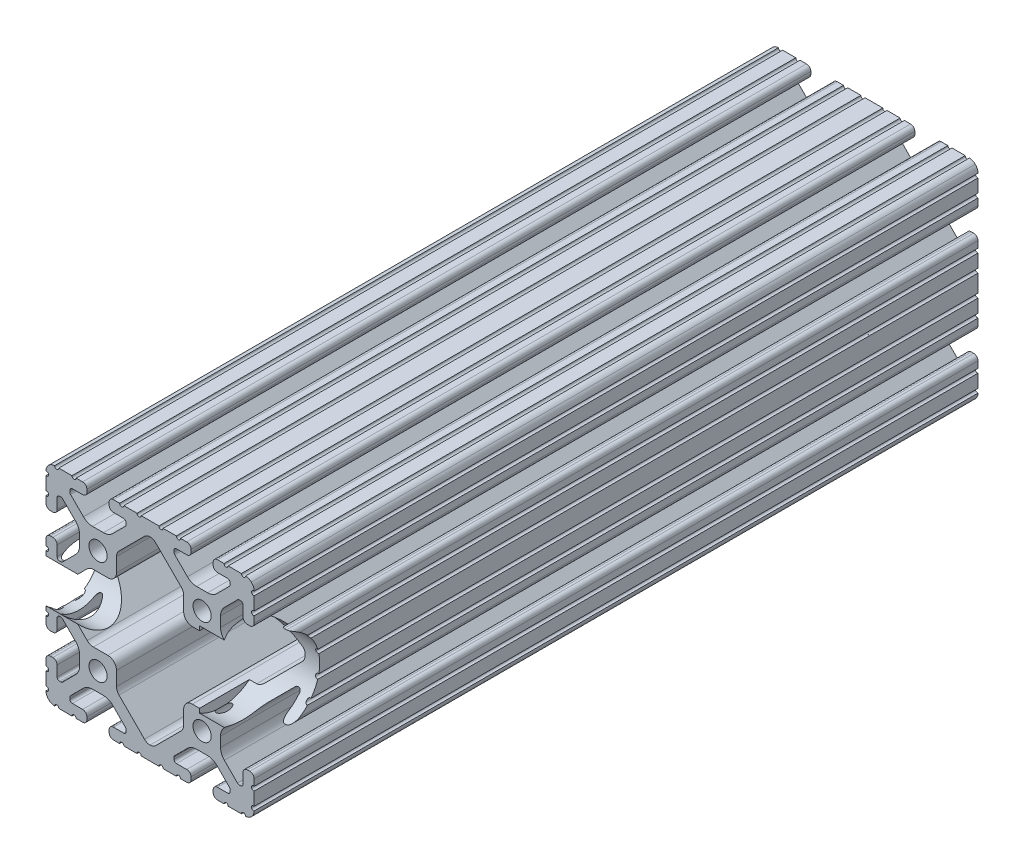
SolidWorks part; units mm, degrees
ref_plane "Front Plane" through (0, 0, 0) normal (0, 0, 1) x (1, 0, 0)
ref_plane "Top Plane" through (0, 0, 0) normal (0, 1, 0) x (1, 0, 0)
ref_plane "Right Plane" through (0, 0, 0) normal (1, 0, 0) x (0, 0, -1)
sketch "Sketch1" plane through (0, 0, 0) normal (0, 0, 1) x (1, 0, 0)
  line L0 (0, 38.1) -> (0, -38.1) construction
  line L1 (-38.1, -38.1) -> (38.1, -38.1) construction
  line L2 (-38.1, -38.1) -> (-38.1, 38.1) construction
  line L3 (-38.1, 38.1) -> (38.1, 38.1) construction
  line L4 (38.1, -38.1) -> (38.1, 38.1) construction
  line L5 (0, 38.1) -> (0, -38.1) construction
  line L6 (-38.1, 0) -> (38.1, 0) construction
  line L7 (-19.05, 19.05) -> (19.05, 19.05) construction
  line L8 (-19.05, 19.05) -> (-19.05, -19.05) construction
  line L9 (-19.05, -19.05) -> (19.05, -19.05) construction
  line L10 (19.05, 19.05) -> (19.05, -19.05) construction
  line L11 (-23.114, 38.1) -> (-23.114, -38.1) construction
  line L12 (-23.114, -38.1) -> (-14.986, 38.1) construction
  line L13 (-14.986, 38.1) -> (-14.986, -38.1) construction
  circle A0 centre (19.05, 19.05) radius 3.3274
  point P0 (0, 0)
  point P9 (0, 0)
  point P12 (-19.05, 0)
  line B0 (-11.3637, -22.8433) -> (-2.0515, -32.1555)
  line B1 (-12.2936, -15.4686) -> (-12.2936, -20.5983)
  line B2 (-20.769, -12.2936) -> (-15.4686, -12.2936)
  line B3 (-31.9021, -2.4756) -> (-23.0141, -11.3637)
  line B4 (-23.0141, 11.3637) -> (-31.9021, 2.4756)
  line B5 (-15.4686, 12.2936) -> (-20.769, 12.2936)
  line B6 (-12.2936, 20.5983) -> (-12.2936, 15.4686)
  line B7 (-2.0515, 32.1555) -> (-11.3637, 22.8433)
  line B8 (11.3637, 22.8433) -> (2.0515, 32.1555)
  line B9 (12.2936, 15.4686) -> (12.2936, 20.5983)
  line B10 (20.769, 12.2936) -> (15.4686, 12.2936)
  line B11 (31.9021, 2.4756) -> (23.0141, 11.3637)
  line B12 (23.0141, -11.3637) -> (31.9021, -2.4756)
  line B13 (15.4686, -12.2936) -> (20.769, -12.2936)
  line B14 (12.2936, -20.5983) -> (12.2936, -15.4686)
  line B15 (2.0515, -32.1555) -> (11.3637, -22.8433)
  line B16 (-4.7773, 38.1) -> (-9.6053, 38.1)
  line B17 (-11.1289, 38.1) -> (-13.4112, 38.1)
  line B18 (-14.986, 36.5252) -> (-14.986, 35.6108)
  line B19 (-13.4112, 34.036) -> (-9.652, 34.036)
  line B20 (-8.763, 33.147) -> (-8.763, 32.4935)
  line B21 (-9.0234, 31.8649) -> (-13.6907, 27.1976)
  line B22 (-17.0493, 25.8064) -> (-21.0507, 25.8064)
  line B23 (-24.4093, 27.1976) -> (-29.1002, 31.8885)
  line B24 (-29.337, 32.7207) -> (-29.337, 33.147)
  line B25 (-28.448, 34.036) -> (-24.6888, 34.036)
  line B26 (-23.114, 35.6108) -> (-23.114, 36.5252)
  line B27 (-24.6888, 38.1) -> (-27.0772, 38.1)
  line B28 (-28.6011, 38.1) -> (-33.4288, 38.1)
  line B29 (-38.1, 33.373) -> (-38.1, 28.5453)
  line B30 (-38.1, 27.0238) -> (-38.1, 24.6302)
  line B31 (-36.5252, 23.0554) -> (-35.6108, 23.0554)
  line B32 (-34.036, 24.6302) -> (-34.036, 28.448)
  line B33 (-33.147, 29.337) -> (-32.6643, 29.337)
  line B34 (-32.0357, 29.0766) -> (-27.1976, 24.2385)
  line B35 (-25.8064, 20.8799) -> (-25.8064, 17.2201)
  line B36 (-27.1976, 13.8615) -> (-31.9489, 9.1101)
  line B37 (-32.7869, 8.763) -> (-33.0603, 8.763)
  line B38 (-34.036, 9.7387) -> (-34.036, 13.4698)
  line B39 (-35.6108, 15.0446) -> (-36.5252, 15.0446)
  line B40 (-38.1, 13.4698) -> (-38.1, 11.075)
  line B41 (-38.1, 9.552) -> (-38.1, 4.7238)
  line B42 (-38.1, 3.2007) -> (-38.1, -3.2007)
  line B43 (-38.1, -4.7238) -> (-38.1, -9.552)
  line B44 (-38.1, -11.075) -> (-38.1, -13.4698)
  line B45 (-36.5252, -15.0446) -> (-35.6108, -15.0446)
  line B46 (-34.036, -13.4698) -> (-34.036, -9.7387)
  line B47 (-33.0603, -8.763) -> (-32.7869, -8.763)
  line B48 (-31.9489, -9.1101) -> (-27.1976, -13.8615)
  line B49 (-25.8064, -17.2201) -> (-25.8064, -20.8799)
  line B50 (-27.1976, -24.2385) -> (-32.0357, -29.0766)
  line B51 (-32.6643, -29.337) -> (-33.147, -29.337)
  line B52 (-34.036, -28.448) -> (-34.036, -24.6302)
  line B53 (-35.6108, -23.0554) -> (-36.5252, -23.0554)
  line B54 (-38.1, -24.6302) -> (-38.1, -27.0238)
  line B55 (-38.1, -28.5453) -> (-38.1, -33.373)
  line B56 (-33.4288, -38.1) -> (-28.6011, -38.1)
  line B57 (-27.0772, -38.1) -> (-24.6888, -38.1)
  line B58 (-23.114, -36.5252) -> (-23.114, -35.6108)
  line B59 (-24.6888, -34.036) -> (-28.448, -34.036)
  line B60 (-29.337, -33.147) -> (-29.337, -32.7207)
  line B61 (-29.1002, -31.8885) -> (-24.4093, -27.1976)
  line B62 (-21.0507, -25.8064) -> (-17.0493, -25.8064)
  line B63 (-13.6907, -27.1976) -> (-9.0234, -31.8649)
  line B64 (-8.763, -32.4935) -> (-8.763, -33.147)
  line B65 (-9.652, -34.036) -> (-13.4112, -34.036)
  line B66 (-14.986, -35.6108) -> (-14.986, -36.5252)
  line B67 (-13.4112, -38.1) -> (-11.1289, -38.1)
  line B68 (-9.6053, -38.1) -> (-4.7773, -38.1)
  line B69 (-3.2537, -38.1) -> (3.2537, -38.1)
  line B70 (4.7773, -38.1) -> (9.6053, -38.1)
  line B71 (11.1289, -38.1) -> (13.4112, -38.1)
  line B72 (14.986, -36.5252) -> (14.986, -35.6108)
  line B73 (13.4112, -34.036) -> (9.652, -34.036)
  line B74 (8.763, -33.147) -> (8.763, -32.4935)
  line B75 (9.0234, -31.8649) -> (13.6907, -27.1976)
  line B76 (17.0493, -25.8064) -> (21.0507, -25.8064)
  line B77 (24.4093, -27.1976) -> (29.1002, -31.8885)
  line B78 (29.337, -32.7207) -> (29.337, -33.147)
  line B79 (28.448, -34.036) -> (24.6888, -34.036)
  line B80 (23.114, -35.6108) -> (23.114, -36.5252)
  line B81 (24.6888, -38.1) -> (27.0772, -38.1)
  line B82 (28.6011, -38.1) -> (33.4288, -38.1)
  line B83 (38.1, -33.373) -> (38.1, -28.5453)
  line B84 (38.1, -27.0238) -> (38.1, -24.6302)
  line B85 (36.5252, -23.0554) -> (35.6108, -23.0554)
  line B86 (34.036, -24.6302) -> (34.036, -28.448)
  line B87 (33.147, -29.337) -> (32.6643, -29.337)
  line B88 (32.0357, -29.0766) -> (27.1976, -24.2385)
  line B89 (25.8064, -20.8799) -> (25.8064, -17.2201)
  line B90 (27.1976, -13.8615) -> (31.9489, -9.1101)
  line B91 (32.7869, -8.763) -> (33.0603, -8.763)
  line B92 (34.036, -9.7387) -> (34.036, -13.4698)
  line B93 (35.6108, -15.0446) -> (36.5252, -15.0446)
  line B94 (38.1, -13.4698) -> (38.1, -11.075)
  line B95 (38.1, -9.552) -> (38.1, -4.7238)
  line B96 (38.1, -3.2007) -> (38.1, 3.2007)
  line B97 (38.1, 4.7238) -> (38.1, 9.552)
  line B98 (38.1, 11.075) -> (38.1, 13.4698)
  line B99 (36.5252, 15.0446) -> (35.6108, 15.0446)
  line B100 (34.036, 13.4698) -> (34.036, 9.7387)
  line B101 (33.0603, 8.763) -> (32.7869, 8.763)
  line B102 (31.9489, 9.1101) -> (27.1976, 13.8615)
  line B103 (25.8064, 17.2201) -> (25.8064, 20.8799)
  line B104 (27.1976, 24.2385) -> (32.0357, 29.0766)
  line B105 (32.6643, 29.337) -> (33.147, 29.337)
  line B106 (34.036, 28.448) -> (34.036, 24.6302)
  line B107 (35.6108, 23.0554) -> (36.5252, 23.0554)
  line B108 (38.1, 24.6302) -> (38.1, 27.0238)
  line B109 (38.1, 28.5453) -> (38.1, 33.373)
  line B110 (33.4288, 38.1) -> (28.6011, 38.1)
  line B111 (27.0772, 38.1) -> (24.6888, 38.1)
  line B112 (23.114, 36.5252) -> (23.114, 35.6108)
  line B113 (24.6888, 34.036) -> (28.448, 34.036)
  line B114 (29.337, 33.147) -> (29.337, 32.7207)
  line B115 (29.1002, 31.8885) -> (24.4093, 27.1976)
  line B116 (21.0507, 25.8064) -> (17.0493, 25.8064)
  line B117 (13.6907, 27.1976) -> (9.0234, 31.8649)
  line B118 (8.763, 32.4935) -> (8.763, 33.147)
  line B119 (9.652, 34.036) -> (13.4112, 34.036)
  line B120 (14.986, 35.6108) -> (14.986, 36.5252)
  line B121 (13.4112, 38.1) -> (11.1289, 38.1)
  line B122 (9.6053, 38.1) -> (4.7773, 38.1)
  line B123 (3.2537, 38.1) -> (-3.2537, 38.1)
  circle B124 centre (-19.05, 19.05) radius 3.3274
  circle B125 centre (-19.05, -19.05) radius 3.3274
  circle B126 centre (19.05, -19.05) radius 3.3274
  circle B127 centre (19.05, 19.05) radius 3.3274
  arc B128 (0, -33.011) -> (2.0515, -32.1555) centre (-0.0139, -30.09) ccw
  arc B129 (-2.0515, -32.1555) -> (0, -33.011) centre (0.0139, -30.09) ccw
  arc B130 (-12.2936, -20.5983) -> (-11.3637, -22.8433) centre (-9.1186, -20.5983) ccw
  arc B131 (-12.2936, -15.4686) -> (-15.4686, -12.2936) centre (-15.4686, -15.4686) ccw
  arc B132 (-23.0141, -11.3637) -> (-20.769, -12.2936) centre (-20.769, -9.1186) ccw
  arc B133 (-32.7287, 0) -> (-31.9021, -2.4756) centre (-29.8367, -0.4102) ccw
  arc B134 (-31.9021, 2.4756) -> (-32.7287, 0) centre (-29.8367, 0.4102) ccw
  arc B135 (-20.769, 12.2936) -> (-23.0141, 11.3637) centre (-20.769, 9.1186) ccw
  arc B136 (-15.4686, 12.2936) -> (-12.2936, 15.4686) centre (-15.4686, 15.4686) ccw
  arc B137 (-11.3637, 22.8433) -> (-12.2936, 20.5983) centre (-9.1186, 20.5983) ccw
  arc B138 (0, 33.011) -> (-2.0515, 32.1555) centre (0.0139, 30.09) ccw
  arc B139 (2.0515, 32.1555) -> (0, 33.011) centre (-0.0139, 30.09) ccw
  arc B140 (12.2936, 20.5983) -> (11.3637, 22.8433) centre (9.1186, 20.5983) ccw
  arc B141 (12.2936, 15.4686) -> (15.4686, 12.2936) centre (15.4686, 15.4686) ccw
  arc B142 (23.0141, 11.3637) -> (20.769, 12.2936) centre (20.769, 9.1186) ccw
  arc B143 (32.7287, 0) -> (31.9021, 2.4756) centre (29.8367, 0.4102) ccw
  arc B144 (31.9021, -2.4756) -> (32.7287, 0) centre (29.8367, -0.4102) ccw
  arc B145 (20.769, -12.2936) -> (23.0141, -11.3637) centre (20.769, -9.1186) ccw
  arc B146 (15.4686, -12.2936) -> (12.2936, -15.4686) centre (15.4686, -15.4686) ccw
  arc B147 (11.3637, -22.8433) -> (12.2936, -20.5983) centre (9.1186, -20.5983) ccw
  arc B148 (-4.7773, 38.1) -> (-3.2537, 38.1) centre (-4.0155, 38.0824) ccw
  arc B149 (-11.1289, 38.1) -> (-9.6053, 38.1) centre (-10.3671, 38.0824) ccw
  arc B150 (-13.4112, 38.1) -> (-14.986, 36.5252) centre (-13.4112, 36.5252) ccw
  arc B151 (-14.986, 35.6108) -> (-13.4112, 34.036) centre (-13.4112, 35.6108) ccw
  arc B152 (-8.763, 33.147) -> (-9.652, 34.036) centre (-9.652, 33.147) ccw
  arc B153 (-9.0234, 31.8649) -> (-8.763, 32.4935) centre (-9.652, 32.4935) ccw
  arc B154 (-17.0493, 25.8064) -> (-13.6907, 27.1976) centre (-17.0493, 30.5562) ccw
  arc B155 (-24.4093, 27.1976) -> (-21.0507, 25.8064) centre (-21.0507, 30.5562) ccw
  arc B156 (-29.337, 32.7207) -> (-29.1002, 31.8885) centre (-28.4716, 32.5172) ccw
  arc B157 (-28.448, 34.036) -> (-29.337, 33.147) centre (-28.448, 33.147) ccw
  arc B158 (-24.6888, 34.036) -> (-23.114, 35.6108) centre (-24.6888, 35.6108) ccw
  arc B159 (-23.114, 36.5252) -> (-24.6888, 38.1) centre (-24.6888, 36.5252) ccw
  arc B160 (-28.6011, 38.1) -> (-27.0772, 38.1) centre (-27.8392, 38.0824) ccw
  arc B161 (-34.9527, 38.1) -> (-33.4288, 38.1) centre (-34.1907, 38.0824) ccw
  arc B162 (-34.9527, 38.1) -> (-37.0861, 37.1826) centre (-34.8521, 34.9266) ccw
  arc B163 (-37.0861, 37.1826) -> (-38.1, 34.8455) centre (-34.925, 34.8566) ccw
  arc B164 (-38.1, 33.373) -> (-38.1, 34.8455) centre (-37.9035, 34.1092) ccw
  arc B165 (-38.1, 27.0238) -> (-38.1, 28.5453) centre (-37.9035, 27.7845) ccw
  arc B166 (-38.1, 24.6302) -> (-36.5252, 23.0554) centre (-36.5252, 24.6302) ccw
  arc B167 (-35.6108, 23.0554) -> (-34.036, 24.6302) centre (-35.6108, 24.6302) ccw
  arc B168 (-33.147, 29.337) -> (-34.036, 28.448) centre (-33.147, 28.448) ccw
  arc B169 (-32.0357, 29.0766) -> (-32.6643, 29.337) centre (-32.6643, 28.448) ccw
  arc B170 (-25.8064, 20.8799) -> (-27.1976, 24.2385) centre (-30.5562, 20.8799) ccw
  arc B171 (-27.1976, 13.8615) -> (-25.8064, 17.2201) centre (-30.5562, 17.2201) ccw
  arc B172 (-32.7869, 8.763) -> (-31.9489, 9.1101) centre (-32.7869, 9.9481) ccw
  arc B173 (-34.036, 9.7387) -> (-33.0603, 8.763) centre (-33.0603, 9.7387) ccw
  arc B174 (-34.036, 13.4698) -> (-35.6108, 15.0446) centre (-35.6108, 13.4698) ccw
  arc B175 (-36.5252, 15.0446) -> (-38.1, 13.4698) centre (-36.5252, 13.4698) ccw
  arc B176 (-38.1, 9.552) -> (-38.1, 11.075) centre (-37.9035, 10.3135) ccw
  arc B177 (-38.1, 3.2007) -> (-38.1, 4.7238) centre (-37.9035, 3.9622) ccw
  arc B178 (-38.1, -4.7238) -> (-38.1, -3.2007) centre (-37.9035, -3.9622) ccw
  arc B179 (-38.1, -11.075) -> (-38.1, -9.552) centre (-37.9035, -10.3135) ccw
  arc B180 (-38.1, -13.4698) -> (-36.5252, -15.0446) centre (-36.5252, -13.4698) ccw
  arc B181 (-35.6108, -15.0446) -> (-34.036, -13.4698) centre (-35.6108, -13.4698) ccw
  arc B182 (-33.0603, -8.763) -> (-34.036, -9.7387) centre (-33.0603, -9.7387) ccw
  arc B183 (-31.9489, -9.1101) -> (-32.7869, -8.763) centre (-32.7869, -9.9481) ccw
  arc B184 (-25.8064, -17.2201) -> (-27.1976, -13.8615) centre (-30.5562, -17.2201) ccw
  arc B185 (-27.1976, -24.2385) -> (-25.8064, -20.8799) centre (-30.5562, -20.8799) ccw
  arc B186 (-32.6643, -29.337) -> (-32.0357, -29.0766) centre (-32.6643, -28.448) ccw
  arc B187 (-34.036, -28.448) -> (-33.147, -29.337) centre (-33.147, -28.448) ccw
  arc B188 (-34.036, -24.6302) -> (-35.6108, -23.0554) centre (-35.6108, -24.6302) ccw
  arc B189 (-36.5252, -23.0554) -> (-38.1, -24.6302) centre (-36.5252, -24.6302) ccw
  arc B190 (-38.1, -28.5453) -> (-38.1, -27.0238) centre (-37.9035, -27.7845) ccw
  arc B191 (-38.1, -34.8455) -> (-38.1, -33.373) centre (-37.9035, -34.1092) ccw
  arc B192 (-38.1, -34.8455) -> (-37.0861, -37.1826) centre (-34.925, -34.8566) ccw
  arc B193 (-37.0861, -37.1826) -> (-34.9527, -38.1) centre (-34.8521, -34.9266) ccw
  arc B194 (-33.4288, -38.1) -> (-34.9527, -38.1) centre (-34.1907, -38.0824) ccw
  arc B195 (-27.0772, -38.1) -> (-28.6011, -38.1) centre (-27.8392, -38.0824) ccw
  arc B196 (-24.6888, -38.1) -> (-23.114, -36.5252) centre (-24.6888, -36.5252) ccw
  arc B197 (-23.114, -35.6108) -> (-24.6888, -34.036) centre (-24.6888, -35.6108) ccw
  arc B198 (-29.337, -33.147) -> (-28.448, -34.036) centre (-28.448, -33.147) ccw
  arc B199 (-29.1002, -31.8885) -> (-29.337, -32.7207) centre (-28.4716, -32.5172) ccw
  arc B200 (-21.0507, -25.8064) -> (-24.4093, -27.1976) centre (-21.0507, -30.5562) ccw
  arc B201 (-13.6907, -27.1976) -> (-17.0493, -25.8064) centre (-17.0493, -30.5562) ccw
  arc B202 (-8.763, -32.4935) -> (-9.0234, -31.8649) centre (-9.652, -32.4935) ccw
  arc B203 (-9.652, -34.036) -> (-8.763, -33.147) centre (-9.652, -33.147) ccw
  arc B204 (-13.4112, -34.036) -> (-14.986, -35.6108) centre (-13.4112, -35.6108) ccw
  arc B205 (-14.986, -36.5252) -> (-13.4112, -38.1) centre (-13.4112, -36.5252) ccw
  arc B206 (-9.6053, -38.1) -> (-11.1289, -38.1) centre (-10.3671, -38.0824) ccw
  arc B207 (-3.2537, -38.1) -> (-4.7773, -38.1) centre (-4.0155, -38.0824) ccw
  arc B208 (4.7773, -38.1) -> (3.2537, -38.1) centre (4.0155, -38.0824) ccw
  arc B209 (11.1289, -38.1) -> (9.6053, -38.1) centre (10.3671, -38.0824) ccw
  arc B210 (13.4112, -38.1) -> (14.986, -36.5252) centre (13.4112, -36.5252) ccw
  arc B211 (14.986, -35.6108) -> (13.4112, -34.036) centre (13.4112, -35.6108) ccw
  arc B212 (8.763, -33.147) -> (9.652, -34.036) centre (9.652, -33.147) ccw
  arc B213 (9.0234, -31.8649) -> (8.763, -32.4935) centre (9.652, -32.4935) ccw
  arc B214 (17.0493, -25.8064) -> (13.6907, -27.1976) centre (17.0493, -30.5562) ccw
  arc B215 (24.4093, -27.1976) -> (21.0507, -25.8064) centre (21.0507, -30.5562) ccw
  arc B216 (29.337, -32.7207) -> (29.1002, -31.8885) centre (28.4716, -32.5172) ccw
  arc B217 (28.448, -34.036) -> (29.337, -33.147) centre (28.448, -33.147) ccw
  arc B218 (24.6888, -34.036) -> (23.114, -35.6108) centre (24.6888, -35.6108) ccw
  arc B219 (23.114, -36.5252) -> (24.6888, -38.1) centre (24.6888, -36.5252) ccw
  arc B220 (28.6011, -38.1) -> (27.0772, -38.1) centre (27.8392, -38.0824) ccw
  arc B221 (34.9527, -38.1) -> (33.4288, -38.1) centre (34.1907, -38.0824) ccw
  arc B222 (34.9527, -38.1) -> (37.0861, -37.1826) centre (34.8521, -34.9266) ccw
  arc B223 (37.0861, -37.1826) -> (38.1, -34.8455) centre (34.925, -34.8566) ccw
  arc B224 (38.1, -33.373) -> (38.1, -34.8455) centre (37.9035, -34.1092) ccw
  arc B225 (38.1, -27.0238) -> (38.1, -28.5453) centre (37.9035, -27.7845) ccw
  arc B226 (38.1, -24.6302) -> (36.5252, -23.0554) centre (36.5252, -24.6302) ccw
  arc B227 (35.6108, -23.0554) -> (34.036, -24.6302) centre (35.6108, -24.6302) ccw
  arc B228 (33.147, -29.337) -> (34.036, -28.448) centre (33.147, -28.448) ccw
  arc B229 (32.0357, -29.0766) -> (32.6643, -29.337) centre (32.6643, -28.448) ccw
  arc B230 (25.8064, -20.8799) -> (27.1976, -24.2385) centre (30.5562, -20.8799) ccw
  arc B231 (27.1976, -13.8615) -> (25.8064, -17.2201) centre (30.5562, -17.2201) ccw
  arc B232 (32.7869, -8.763) -> (31.9489, -9.1101) centre (32.7869, -9.9481) ccw
  arc B233 (34.036, -9.7387) -> (33.0603, -8.763) centre (33.0603, -9.7387) ccw
  arc B234 (34.036, -13.4698) -> (35.6108, -15.0446) centre (35.6108, -13.4698) ccw
  arc B235 (36.5252, -15.0446) -> (38.1, -13.4698) centre (36.5252, -13.4698) ccw
  arc B236 (38.1, -9.552) -> (38.1, -11.075) centre (37.9035, -10.3135) ccw
  arc B237 (38.1, -3.2007) -> (38.1, -4.7238) centre (37.9035, -3.9622) ccw
  arc B238 (38.1, 4.7238) -> (38.1, 3.2007) centre (37.9035, 3.9622) ccw
  arc B239 (38.1, 11.075) -> (38.1, 9.552) centre (37.9035, 10.3135) ccw
  arc B240 (38.1, 13.4698) -> (36.5252, 15.0446) centre (36.5252, 13.4698) ccw
  arc B241 (35.6108, 15.0446) -> (34.036, 13.4698) centre (35.6108, 13.4698) ccw
  arc B242 (33.0603, 8.763) -> (34.036, 9.7387) centre (33.0603, 9.7387) ccw
  arc B243 (31.9489, 9.1101) -> (32.7869, 8.763) centre (32.7869, 9.9481) ccw
  arc B244 (25.8064, 17.2201) -> (27.1976, 13.8615) centre (30.5562, 17.2201) ccw
  arc B245 (27.1976, 24.2385) -> (25.8064, 20.8799) centre (30.5562, 20.8799) ccw
  arc B246 (32.6643, 29.337) -> (32.0357, 29.0766) centre (32.6643, 28.448) ccw
  arc B247 (34.036, 28.448) -> (33.147, 29.337) centre (33.147, 28.448) ccw
  arc B248 (34.036, 24.6302) -> (35.6108, 23.0554) centre (35.6108, 24.6302) ccw
  arc B249 (36.5252, 23.0554) -> (38.1, 24.6302) centre (36.5252, 24.6302) ccw
  arc B250 (38.1, 28.5453) -> (38.1, 27.0238) centre (37.9035, 27.7845) ccw
  arc B251 (38.1, 34.8455) -> (38.1, 33.373) centre (37.9035, 34.1092) ccw
  arc B252 (38.1, 34.8455) -> (37.0861, 37.1826) centre (34.925, 34.8566) ccw
  arc B253 (37.0861, 37.1826) -> (34.9527, 38.1) centre (34.8521, 34.9266) ccw
  arc B254 (33.4288, 38.1) -> (34.9527, 38.1) centre (34.1907, 38.0824) ccw
  arc B255 (27.0772, 38.1) -> (28.6011, 38.1) centre (27.8392, 38.0824) ccw
  arc B256 (24.6888, 38.1) -> (23.114, 36.5252) centre (24.6888, 36.5252) ccw
  arc B257 (23.114, 35.6108) -> (24.6888, 34.036) centre (24.6888, 35.6108) ccw
  arc B258 (29.337, 33.147) -> (28.448, 34.036) centre (28.448, 33.147) ccw
  arc B259 (29.1002, 31.8885) -> (29.337, 32.7207) centre (28.4716, 32.5172) ccw
  arc B260 (21.0507, 25.8064) -> (24.4093, 27.1976) centre (21.0507, 30.5562) ccw
  arc B261 (13.6907, 27.1976) -> (17.0493, 25.8064) centre (17.0493, 30.5562) ccw
  arc B262 (8.763, 32.4935) -> (9.0234, 31.8649) centre (9.652, 32.4935) ccw
  arc B263 (9.652, 34.036) -> (8.763, 33.147) centre (9.652, 33.147) ccw
  arc B264 (13.4112, 34.036) -> (14.986, 35.6108) centre (13.4112, 35.6108) ccw
  arc B265 (14.986, 36.5252) -> (13.4112, 38.1) centre (13.4112, 36.5252) ccw
  arc B266 (9.6053, 38.1) -> (11.1289, 38.1) centre (10.3671, 38.0824) ccw
  arc B267 (3.2537, 38.1) -> (4.7773, 38.1) centre (4.0155, 38.0824) ccw
  dimension "Center Hole Diameter" = 6.6548
  dimension "Rail Width" = 76.2
  dimension "Rail Height" = 76.2
  dimension "T-Slot Width" = 8.128
sketch_block_instance "Block1-1"
sketch_block "Block1"
sketch "Sketch2" plane through (0, 0, 0) normal (1, 0, 0) x (0, 0, -1)
  line L0 (-132.5, 0) -> (132.5, 0) construction
  line L1 (-132.5, 38.1) -> (-132.5, -38.1) construction
  line L2 (-132.5, -38.1) -> (132.5, -38.1) construction
  line L3 (132.5, -38.1) -> (132.5, 38.1) construction
  line L4 (-30.9, 0) -> (-30.9, 38.1) construction
  line L5 (-30.9, 38.1) -> (30.9, 38.1) construction
  line L6 (30.9, 38.1) -> (30.9, 0) construction
  point P5 (30.9, 0)
  point P10 (-30.9, 0)
  dimension "D1" = 101.6
  dimension "Length" = 265
  dimension "D2" = 101.6
sketch "Sketch3" plane through (0, 0, 0) normal (0, 0, 1) x (1, 0, 0)
  line L0 (-11.3637, -22.8433) -> (-2.0515, -32.1555) construction
  line L1 (-12.2936, -15.4686) -> (-12.2936, -20.5983) construction
  line L2 (-20.769, -12.2936) -> (-15.4686, -12.2936) construction
  line L3 (-31.9021, -2.4756) -> (-23.0141, -11.3637) construction
  line L4 (-23.0141, 11.3637) -> (-31.9021, 2.4756) construction
  line L5 (-15.4686, 12.2936) -> (-20.769, 12.2936) construction
  line L6 (-12.2936, 20.5983) -> (-12.2936, 15.4686) construction
  line L7 (-2.0515, 32.1555) -> (-11.3637, 22.8433) construction
  line L8 (11.3637, 22.8433) -> (2.0515, 32.1555) construction
  line L9 (12.2936, 15.4686) -> (12.2936, 20.5983) construction
  line L10 (20.769, 12.2936) -> (15.4686, 12.2936) construction
  line L11 (31.9021, 2.4756) -> (23.0141, 11.3637) construction
  line L12 (23.0141, -11.3637) -> (31.9021, -2.4756) construction
  line L13 (15.4686, -12.2936) -> (20.769, -12.2936) construction
  line L14 (12.2936, -20.5983) -> (12.2936, -15.4686) construction
  line L15 (2.0515, -32.1555) -> (11.3637, -22.8433) construction
  line L16 (34.036, 28.448) -> (34.036, 24.6302) construction
  line L17 (35.6108, 23.0554) -> (36.5252, 23.0554) construction
  line L18 (38.1, 24.6302) -> (38.1, 27.0238) construction
  line L19 (38.1, 28.5453) -> (38.1, 33.373) construction
  line L20 (33.4288, 38.1) -> (28.6011, 38.1) construction
  line L21 (27.0772, 38.1) -> (24.6888, 38.1) construction
  line L22 (23.114, 36.5252) -> (23.114, 35.6108) construction
  line L23 (24.6888, 34.036) -> (28.448, 34.036) construction
  line L24 (29.337, 33.147) -> (29.337, 32.7207) construction
  line L25 (29.1002, 31.8885) -> (24.4093, 27.1976) construction
  line L26 (21.0507, 25.8064) -> (17.0493, 25.8064) construction
  line L27 (13.6907, 27.1976) -> (9.0234, 31.8649) construction
  line L28 (8.763, 32.4935) -> (8.763, 33.147) construction
  line L29 (9.652, 34.036) -> (13.4112, 34.036) construction
  line L30 (14.986, 35.6108) -> (14.986, 36.5252) construction
  line L31 (13.4112, 38.1) -> (11.1289, 38.1) construction
  line L32 (9.6053, 38.1) -> (4.7773, 38.1) construction
  line L33 (3.2537, 38.1) -> (-3.2537, 38.1) construction
  line L34 (-4.7773, 38.1) -> (-9.6053, 38.1) construction
  line L35 (-11.1289, 38.1) -> (-13.4112, 38.1) construction
  line L36 (-14.986, 36.5252) -> (-14.986, 35.6108) construction
  line L37 (-13.4112, 34.036) -> (-9.652, 34.036) construction
  line L38 (-8.763, 33.147) -> (-8.763, 32.4935) construction
  line L39 (-9.0234, 31.8649) -> (-13.6907, 27.1976) construction
  line L40 (-17.0493, 25.8064) -> (-21.0507, 25.8064) construction
  line L41 (-24.4093, 27.1976) -> (-29.1002, 31.8885) construction
  line L42 (-29.337, 32.7207) -> (-29.337, 33.147) construction
  line L43 (-28.448, 34.036) -> (-24.6888, 34.036) construction
  line L44 (-23.114, 35.6108) -> (-23.114, 36.5252) construction
  line L45 (-24.6888, 38.1) -> (-27.0772, 38.1) construction
  line L46 (-28.6011, 38.1) -> (-33.4288, 38.1) construction
  line L47 (-38.1, 33.373) -> (-38.1, 28.5453) construction
  line L48 (-38.1, 27.0238) -> (-38.1, 24.6302) construction
  line L49 (-36.5252, 23.0554) -> (-35.6108, 23.0554) construction
  line L50 (-34.036, 24.6302) -> (-34.036, 28.448) construction
  line L51 (-33.147, 29.337) -> (-32.6643, 29.337) construction
  line L52 (-32.0357, 29.0766) -> (-27.1976, 24.2385) construction
  line L53 (-25.8064, 20.8799) -> (-25.8064, 17.2201) construction
  line L54 (-27.1976, 13.8615) -> (-31.9489, 9.1101) construction
  line L55 (-32.7869, 8.763) -> (-33.0603, 8.763) construction
  line L56 (-34.036, 9.7387) -> (-34.036, 13.4698) construction
  line L57 (-35.6108, 15.0446) -> (-36.5252, 15.0446) construction
  line L58 (-38.1, 13.4698) -> (-38.1, 11.075) construction
  line L59 (-38.1, 9.552) -> (-38.1, 4.7238) construction
  line L60 (-38.1, 3.2007) -> (-38.1, -3.2007) construction
  line L61 (-38.1, -4.7238) -> (-38.1, -9.552) construction
  line L62 (-38.1, -11.075) -> (-38.1, -13.4698) construction
  line L63 (-36.5252, -15.0446) -> (-35.6108, -15.0446) construction
  line L64 (-34.036, -13.4698) -> (-34.036, -9.7387) construction
  line L65 (-33.0603, -8.763) -> (-32.7869, -8.763) construction
  line L66 (-31.9489, -9.1101) -> (-27.1976, -13.8615) construction
  line L67 (-25.8064, -17.2201) -> (-25.8064, -20.8799) construction
  line L68 (-27.1976, -24.2385) -> (-32.0357, -29.0766) construction
  line L69 (-32.6643, -29.337) -> (-33.147, -29.337) construction
  line L70 (-34.036, -28.448) -> (-34.036, -24.6302) construction
  line L71 (-35.6108, -23.0554) -> (-36.5252, -23.0554) construction
  line L72 (-38.1, -24.6302) -> (-38.1, -27.0238) construction
  line L73 (-38.1, -28.5453) -> (-38.1, -33.373) construction
  line L74 (-33.4288, -38.1) -> (-28.6011, -38.1) construction
  line L75 (-27.0772, -38.1) -> (-24.6888, -38.1) construction
  line L76 (-23.114, -36.5252) -> (-23.114, -35.6108) construction
  line L77 (-24.6888, -34.036) -> (-28.448, -34.036) construction
  line L78 (-29.337, -33.147) -> (-29.337, -32.7207) construction
  line L79 (-29.1002, -31.8885) -> (-24.4093, -27.1976) construction
  line L80 (-21.0507, -25.8064) -> (-17.0493, -25.8064) construction
  line L81 (-13.6907, -27.1976) -> (-9.0234, -31.8649) construction
  line L82 (-8.763, -32.4935) -> (-8.763, -33.147) construction
  line L83 (-9.652, -34.036) -> (-13.4112, -34.036) construction
  line L84 (-14.986, -35.6108) -> (-14.986, -36.5252) construction
  line L85 (-13.4112, -38.1) -> (-11.1289, -38.1) construction
  line L86 (-9.6053, -38.1) -> (-4.7773, -38.1) construction
  line L87 (-3.2537, -38.1) -> (3.2537, -38.1) construction
  line L88 (4.7773, -38.1) -> (9.6053, -38.1) construction
  line L89 (11.1289, -38.1) -> (13.4112, -38.1) construction
  line L90 (14.986, -36.5252) -> (14.986, -35.6108) construction
  line L91 (13.4112, -34.036) -> (9.652, -34.036) construction
  line L92 (8.763, -33.147) -> (8.763, -32.4935) construction
  line L93 (9.0234, -31.8649) -> (13.6907, -27.1976) construction
  line L94 (17.0493, -25.8064) -> (21.0507, -25.8064) construction
  line L95 (24.4093, -27.1976) -> (29.1002, -31.8885) construction
  line L96 (29.337, -32.7207) -> (29.337, -33.147) construction
  line L97 (28.448, -34.036) -> (24.6888, -34.036) construction
  line L98 (23.114, -35.6108) -> (23.114, -36.5252) construction
  line L99 (24.6888, -38.1) -> (27.0772, -38.1) construction
  line L100 (28.6011, -38.1) -> (33.4288, -38.1) construction
  line L101 (38.1, -33.373) -> (38.1, -28.5453) construction
  line L102 (38.1, -27.0238) -> (38.1, -24.6302) construction
  line L103 (36.5252, -23.0554) -> (35.6108, -23.0554) construction
  line L104 (34.036, -24.6302) -> (34.036, -28.448) construction
  line L105 (33.147, -29.337) -> (32.6643, -29.337) construction
  line L106 (32.0357, -29.0766) -> (27.1976, -24.2385) construction
  line L107 (25.8064, -20.8799) -> (25.8064, -17.2201) construction
  line L108 (27.1976, -13.8615) -> (31.9489, -9.1101) construction
  line L109 (32.7869, -8.763) -> (33.0603, -8.763) construction
  line L110 (34.036, -9.7387) -> (34.036, -13.4698) construction
  line L111 (35.6108, -15.0446) -> (36.5252, -15.0446) construction
  line L112 (38.1, -13.4698) -> (38.1, -11.075) construction
  line L113 (38.1, -9.552) -> (38.1, -4.7238) construction
  line L114 (38.1, -3.2007) -> (38.1, 3.2007) construction
  line L115 (38.1, 4.7238) -> (38.1, 9.552) construction
  line L116 (38.1, 11.075) -> (38.1, 13.4698) construction
  line L117 (36.5252, 15.0446) -> (35.6108, 15.0446) construction
  line L118 (34.036, 13.4698) -> (34.036, 9.7387) construction
  line L119 (33.0603, 8.763) -> (32.7869, 8.763) construction
  line L120 (31.9489, 9.1101) -> (27.1976, 13.8615) construction
  line L121 (25.8064, 17.2201) -> (25.8064, 20.8799) construction
  line L122 (27.1976, 24.2385) -> (32.0357, 29.0766) construction
  line L123 (32.6643, 29.337) -> (33.147, 29.337) construction
  line L124 (-11.3637, -22.8433) -> (-2.0515, -32.1555)
  line L125 (-12.2936, -15.4686) -> (-12.2936, -20.5983)
  line L126 (-20.769, -12.2936) -> (-15.4686, -12.2936)
  line L127 (-31.9021, -2.4756) -> (-23.0141, -11.3637)
  line L128 (-23.0141, 11.3637) -> (-31.9021, 2.4756)
  line L129 (-15.4686, 12.2936) -> (-20.769, 12.2936)
  line L130 (-12.2936, 20.5983) -> (-12.2936, 15.4686)
  line L131 (-2.0515, 32.1555) -> (-11.3637, 22.8433)
  line L132 (11.3637, 22.8433) -> (2.0515, 32.1555)
  line L133 (12.2936, 15.4686) -> (12.2936, 20.5983)
  line L134 (20.769, 12.2936) -> (15.4686, 12.2936)
  line L135 (31.9021, 2.4756) -> (23.0141, 11.3637)
  line L136 (23.0141, -11.3637) -> (31.9021, -2.4756)
  line L137 (15.4686, -12.2936) -> (20.769, -12.2936)
  line L138 (12.2936, -20.5983) -> (12.2936, -15.4686)
  line L139 (2.0515, -32.1555) -> (11.3637, -22.8433)
  line L140 (34.036, 28.448) -> (34.036, 24.6302)
  line L141 (35.6108, 23.0554) -> (36.5252, 23.0554)
  line L142 (38.1, 24.6302) -> (38.1, 27.0238)
  line L143 (38.1, 28.5453) -> (38.1, 33.373)
  line L144 (33.4288, 38.1) -> (28.6011, 38.1)
  line L145 (27.0772, 38.1) -> (24.6888, 38.1)
  line L146 (23.114, 36.5252) -> (23.114, 35.6108)
  line L147 (24.6888, 34.036) -> (28.448, 34.036)
  line L148 (29.337, 33.147) -> (29.337, 32.7207)
  line L149 (29.1002, 31.8885) -> (24.4093, 27.1976)
  line L150 (21.0507, 25.8064) -> (17.0493, 25.8064)
  line L151 (13.6907, 27.1976) -> (9.0234, 31.8649)
  line L152 (8.763, 32.4935) -> (8.763, 33.147)
  line L153 (9.652, 34.036) -> (13.4112, 34.036)
  line L154 (14.986, 35.6108) -> (14.986, 36.5252)
  line L155 (13.4112, 38.1) -> (11.1289, 38.1)
  line L156 (9.6053, 38.1) -> (4.7773, 38.1)
  line L157 (3.2537, 38.1) -> (-3.2537, 38.1)
  line L158 (-4.7773, 38.1) -> (-9.6053, 38.1)
  line L159 (-11.1289, 38.1) -> (-13.4112, 38.1)
  line L160 (-14.986, 36.5252) -> (-14.986, 35.6108)
  line L161 (-13.4112, 34.036) -> (-9.652, 34.036)
  line L162 (-8.763, 33.147) -> (-8.763, 32.4935)
  line L163 (-9.0234, 31.8649) -> (-13.6907, 27.1976)
  line L164 (-17.0493, 25.8064) -> (-21.0507, 25.8064)
  line L165 (-24.4093, 27.1976) -> (-29.1002, 31.8885)
  line L166 (-29.337, 32.7207) -> (-29.337, 33.147)
  line L167 (-28.448, 34.036) -> (-24.6888, 34.036)
  line L168 (-23.114, 35.6108) -> (-23.114, 36.5252)
  line L169 (-24.6888, 38.1) -> (-27.0772, 38.1)
  line L170 (-28.6011, 38.1) -> (-33.4288, 38.1)
  line L171 (-38.1, 33.373) -> (-38.1, 28.5453)
  line L172 (-38.1, 27.0238) -> (-38.1, 24.6302)
  line L173 (-36.5252, 23.0554) -> (-35.6108, 23.0554)
  line L174 (-34.036, 24.6302) -> (-34.036, 28.448)
  line L175 (-33.147, 29.337) -> (-32.6643, 29.337)
  line L176 (-32.0357, 29.0766) -> (-27.1976, 24.2385)
  line L177 (-25.8064, 20.8799) -> (-25.8064, 17.2201)
  line L178 (-27.1976, 13.8615) -> (-31.9489, 9.1101)
  line L179 (-32.7869, 8.763) -> (-33.0603, 8.763)
  line L180 (-34.036, 9.7387) -> (-34.036, 13.4698)
  line L181 (-35.6108, 15.0446) -> (-36.5252, 15.0446)
  line L182 (-38.1, 13.4698) -> (-38.1, 11.075)
  line L183 (-38.1, 9.552) -> (-38.1, 4.7238)
  line L184 (-38.1, 3.2007) -> (-38.1, -3.2007)
  line L185 (-38.1, -4.7238) -> (-38.1, -9.552)
  line L186 (-38.1, -11.075) -> (-38.1, -13.4698)
  line L187 (-36.5252, -15.0446) -> (-35.6108, -15.0446)
  line L188 (-34.036, -13.4698) -> (-34.036, -9.7387)
  line L189 (-33.0603, -8.763) -> (-32.7869, -8.763)
  line L190 (-31.9489, -9.1101) -> (-27.1976, -13.8615)
  line L191 (-25.8064, -17.2201) -> (-25.8064, -20.8799)
  line L192 (-27.1976, -24.2385) -> (-32.0357, -29.0766)
  line L193 (-32.6643, -29.337) -> (-33.147, -29.337)
  line L194 (-34.036, -28.448) -> (-34.036, -24.6302)
  line L195 (-35.6108, -23.0554) -> (-36.5252, -23.0554)
  line L196 (-38.1, -24.6302) -> (-38.1, -27.0238)
  line L197 (-38.1, -28.5453) -> (-38.1, -33.373)
  line L198 (-33.4288, -38.1) -> (-28.6011, -38.1)
  line L199 (-27.0772, -38.1) -> (-24.6888, -38.1)
  line L200 (-23.114, -36.5252) -> (-23.114, -35.6108)
  line L201 (-24.6888, -34.036) -> (-28.448, -34.036)
  line L202 (-29.337, -33.147) -> (-29.337, -32.7207)
  line L203 (-29.1002, -31.8885) -> (-24.4093, -27.1976)
  line L204 (-21.0507, -25.8064) -> (-17.0493, -25.8064)
  line L205 (-13.6907, -27.1976) -> (-9.0234, -31.8649)
  line L206 (-8.763, -32.4935) -> (-8.763, -33.147)
  line L207 (-9.652, -34.036) -> (-13.4112, -34.036)
  line L208 (-14.986, -35.6108) -> (-14.986, -36.5252)
  line L209 (-13.4112, -38.1) -> (-11.1289, -38.1)
  line L210 (-9.6053, -38.1) -> (-4.7773, -38.1)
  line L211 (-3.2537, -38.1) -> (3.2537, -38.1)
  line L212 (4.7773, -38.1) -> (9.6053, -38.1)
  line L213 (11.1289, -38.1) -> (13.4112, -38.1)
  line L214 (14.986, -36.5252) -> (14.986, -35.6108)
  line L215 (13.4112, -34.036) -> (9.652, -34.036)
  line L216 (8.763, -33.147) -> (8.763, -32.4935)
  line L217 (9.0234, -31.8649) -> (13.6907, -27.1976)
  line L218 (17.0493, -25.8064) -> (21.0507, -25.8064)
  line L219 (24.4093, -27.1976) -> (29.1002, -31.8885)
  line L220 (29.337, -32.7207) -> (29.337, -33.147)
  line L221 (28.448, -34.036) -> (24.6888, -34.036)
  line L222 (23.114, -35.6108) -> (23.114, -36.5252)
  line L223 (24.6888, -38.1) -> (27.0772, -38.1)
  line L224 (28.6011, -38.1) -> (33.4288, -38.1)
  line L225 (38.1, -33.373) -> (38.1, -28.5453)
  line L226 (38.1, -27.0238) -> (38.1, -24.6302)
  line L227 (36.5252, -23.0554) -> (35.6108, -23.0554)
  line L228 (34.036, -24.6302) -> (34.036, -28.448)
  line L229 (33.147, -29.337) -> (32.6643, -29.337)
  line L230 (32.0357, -29.0766) -> (27.1976, -24.2385)
  line L231 (25.8064, -20.8799) -> (25.8064, -17.2201)
  line L232 (27.1976, -13.8615) -> (31.9489, -9.1101)
  line L233 (32.7869, -8.763) -> (33.0603, -8.763)
  line L234 (34.036, -9.7387) -> (34.036, -13.4698)
  line L235 (35.6108, -15.0446) -> (36.5252, -15.0446)
  line L236 (38.1, -13.4698) -> (38.1, -11.075)
  line L237 (38.1, -9.552) -> (38.1, -4.7238)
  line L238 (38.1, -3.2007) -> (38.1, 3.2007)
  line L239 (38.1, 4.7238) -> (38.1, 9.552)
  line L240 (38.1, 11.075) -> (38.1, 13.4698)
  line L241 (36.5252, 15.0446) -> (35.6108, 15.0446)
  line L242 (34.036, 13.4698) -> (34.036, 9.7387)
  line L243 (33.0603, 8.763) -> (32.7869, 8.763)
  line L244 (31.9489, 9.1101) -> (27.1976, 13.8615)
  line L245 (25.8064, 17.2201) -> (25.8064, 20.8799)
  line L246 (27.1976, 24.2385) -> (32.0357, 29.0766)
  line L247 (32.6643, 29.337) -> (33.147, 29.337)
  arc A0 (-2.0515, -32.1555) -> (0, -33.011) centre (0.0139, -30.09) ccw construction
  circle A1 centre (19.05, 19.05) radius 3.3274
  circle A2 centre (19.05, 19.05) radius 3.3274
  arc A3 (-12.2936, -20.5983) -> (-11.3637, -22.8433) centre (-9.1186, -20.5983) ccw construction
  arc A4 (-12.2936, -15.4686) -> (-15.4686, -12.2936) centre (-15.4686, -15.4686) ccw construction
  arc A5 (-23.0141, -11.3637) -> (-20.769, -12.2936) centre (-20.769, -9.1186) ccw construction
  arc A6 (-32.7287, 0) -> (-31.9021, -2.4756) centre (-29.8367, -0.4102) ccw construction
  arc A7 (-31.9021, 2.4756) -> (-32.7287, 0) centre (-29.8367, 0.4102) ccw construction
  arc A8 (-20.769, 12.2936) -> (-23.0141, 11.3637) centre (-20.769, 9.1186) ccw construction
  arc A9 (-15.4686, 12.2936) -> (-12.2936, 15.4686) centre (-15.4686, 15.4686) ccw construction
  arc A10 (-11.3637, 22.8433) -> (-12.2936, 20.5983) centre (-9.1186, 20.5983) ccw construction
  arc A11 (0, 33.011) -> (-2.0515, 32.1555) centre (0.0139, 30.09) ccw construction
  arc A12 (2.0515, 32.1555) -> (0, 33.011) centre (-0.0139, 30.09) ccw construction
  arc A13 (12.2936, 20.5983) -> (11.3637, 22.8433) centre (9.1186, 20.5983) ccw construction
  arc A14 (12.2936, 15.4686) -> (15.4686, 12.2936) centre (15.4686, 15.4686) ccw construction
  arc A15 (23.0141, 11.3637) -> (20.769, 12.2936) centre (20.769, 9.1186) ccw construction
  arc A16 (32.7287, 0) -> (31.9021, 2.4756) centre (29.8367, 0.4102) ccw construction
  arc A17 (31.9021, -2.4756) -> (32.7287, 0) centre (29.8367, -0.4102) ccw construction
  arc A18 (20.769, -12.2936) -> (23.0141, -11.3637) centre (20.769, -9.1186) ccw construction
  arc A19 (15.4686, -12.2936) -> (12.2936, -15.4686) centre (15.4686, -15.4686) ccw construction
  arc A20 (11.3637, -22.8433) -> (12.2936, -20.5983) centre (9.1186, -20.5983) ccw construction
  arc A21 (0, -33.011) -> (2.0515, -32.1555) centre (-0.0139, -30.09) ccw construction
  circle A22 centre (-19.05, 19.05) radius 3.3274 construction
  circle A23 centre (19.05, -19.05) radius 3.3274 construction
  circle A24 centre (-19.05, -19.05) radius 3.3274 construction
  circle A25 centre (19.05, 19.05) radius 3.3274 construction
  arc A26 (34.036, 24.6302) -> (35.6108, 23.0554) centre (35.6108, 24.6302) ccw construction
  arc A27 (36.5252, 23.0554) -> (38.1, 24.6302) centre (36.5252, 24.6302) ccw construction
  arc A28 (38.1, 28.5453) -> (38.1, 27.0238) centre (37.9035, 27.7845) ccw construction
  arc A29 (38.1, 34.8455) -> (38.1, 33.373) centre (37.9035, 34.1092) ccw construction
  arc A30 (38.1, 34.8455) -> (37.0861, 37.1826) centre (34.925, 34.8566) ccw construction
  arc A31 (37.0861, 37.1826) -> (34.9527, 38.1) centre (34.8521, 34.9266) ccw construction
  arc A32 (33.4288, 38.1) -> (34.9527, 38.1) centre (34.1907, 38.0824) ccw construction
  arc A33 (27.0772, 38.1) -> (28.6011, 38.1) centre (27.8392, 38.0824) ccw construction
  arc A34 (24.6888, 38.1) -> (23.114, 36.5252) centre (24.6888, 36.5252) ccw construction
  arc A35 (23.114, 35.6108) -> (24.6888, 34.036) centre (24.6888, 35.6108) ccw construction
  arc A36 (29.337, 33.147) -> (28.448, 34.036) centre (28.448, 33.147) ccw construction
  arc A37 (29.1002, 31.8885) -> (29.337, 32.7207) centre (28.4716, 32.5172) ccw construction
  arc A38 (21.0507, 25.8064) -> (24.4093, 27.1976) centre (21.0507, 30.5562) ccw construction
  arc A39 (13.6907, 27.1976) -> (17.0493, 25.8064) centre (17.0493, 30.5562) ccw construction
  arc A40 (8.763, 32.4935) -> (9.0234, 31.8649) centre (9.652, 32.4935) ccw construction
  arc A41 (9.652, 34.036) -> (8.763, 33.147) centre (9.652, 33.147) ccw construction
  arc A42 (13.4112, 34.036) -> (14.986, 35.6108) centre (13.4112, 35.6108) ccw construction
  arc A43 (14.986, 36.5252) -> (13.4112, 38.1) centre (13.4112, 36.5252) ccw construction
  arc A44 (9.6053, 38.1) -> (11.1289, 38.1) centre (10.3671, 38.0824) ccw construction
  arc A45 (3.2537, 38.1) -> (4.7773, 38.1) centre (4.0155, 38.0824) ccw construction
  arc A46 (-4.7773, 38.1) -> (-3.2537, 38.1) centre (-4.0155, 38.0824) ccw construction
  arc A47 (-11.1289, 38.1) -> (-9.6053, 38.1) centre (-10.3671, 38.0824) ccw construction
  arc A48 (-13.4112, 38.1) -> (-14.986, 36.5252) centre (-13.4112, 36.5252) ccw construction
  arc A49 (-14.986, 35.6108) -> (-13.4112, 34.036) centre (-13.4112, 35.6108) ccw construction
  arc A50 (-8.763, 33.147) -> (-9.652, 34.036) centre (-9.652, 33.147) ccw construction
  arc A51 (-9.0234, 31.8649) -> (-8.763, 32.4935) centre (-9.652, 32.4935) ccw construction
  arc A52 (-17.0493, 25.8064) -> (-13.6907, 27.1976) centre (-17.0493, 30.5562) ccw construction
  arc A53 (-24.4093, 27.1976) -> (-21.0507, 25.8064) centre (-21.0507, 30.5562) ccw construction
  arc A54 (-29.337, 32.7207) -> (-29.1002, 31.8885) centre (-28.4716, 32.5172) ccw construction
  arc A55 (-28.448, 34.036) -> (-29.337, 33.147) centre (-28.448, 33.147) ccw construction
  arc A56 (-24.6888, 34.036) -> (-23.114, 35.6108) centre (-24.6888, 35.6108) ccw construction
  arc A57 (-23.114, 36.5252) -> (-24.6888, 38.1) centre (-24.6888, 36.5252) ccw construction
  arc A58 (-28.6011, 38.1) -> (-27.0772, 38.1) centre (-27.8392, 38.0824) ccw construction
  arc A59 (-34.9527, 38.1) -> (-33.4288, 38.1) centre (-34.1907, 38.0824) ccw construction
  arc A60 (-34.9527, 38.1) -> (-37.0861, 37.1826) centre (-34.8521, 34.9266) ccw construction
  arc A61 (-37.0861, 37.1826) -> (-38.1, 34.8455) centre (-34.925, 34.8566) ccw construction
  arc A62 (-38.1, 33.373) -> (-38.1, 34.8455) centre (-37.9035, 34.1092) ccw construction
  arc A63 (-38.1, 27.0238) -> (-38.1, 28.5453) centre (-37.9035, 27.7845) ccw construction
  arc A64 (-38.1, 24.6302) -> (-36.5252, 23.0554) centre (-36.5252, 24.6302) ccw construction
  arc A65 (-35.6108, 23.0554) -> (-34.036, 24.6302) centre (-35.6108, 24.6302) ccw construction
  arc A66 (-33.147, 29.337) -> (-34.036, 28.448) centre (-33.147, 28.448) ccw construction
  arc A67 (-32.0357, 29.0766) -> (-32.6643, 29.337) centre (-32.6643, 28.448) ccw construction
  arc A68 (-25.8064, 20.8799) -> (-27.1976, 24.2385) centre (-30.5562, 20.8799) ccw construction
  arc A69 (-27.1976, 13.8615) -> (-25.8064, 17.2201) centre (-30.5562, 17.2201) ccw construction
  arc A70 (-32.7869, 8.763) -> (-31.9489, 9.1101) centre (-32.7869, 9.9481) ccw construction
  arc A71 (-34.036, 9.7387) -> (-33.0603, 8.763) centre (-33.0603, 9.7387) ccw construction
  arc A72 (-34.036, 13.4698) -> (-35.6108, 15.0446) centre (-35.6108, 13.4698) ccw construction
  arc A73 (-36.5252, 15.0446) -> (-38.1, 13.4698) centre (-36.5252, 13.4698) ccw construction
  arc A74 (-38.1, 9.552) -> (-38.1, 11.075) centre (-37.9035, 10.3135) ccw construction
  arc A75 (-38.1, 3.2007) -> (-38.1, 4.7238) centre (-37.9035, 3.9622) ccw construction
  arc A76 (-38.1, -4.7238) -> (-38.1, -3.2007) centre (-37.9035, -3.9622) ccw construction
  arc A77 (-38.1, -11.075) -> (-38.1, -9.552) centre (-37.9035, -10.3135) ccw construction
  arc A78 (-38.1, -13.4698) -> (-36.5252, -15.0446) centre (-36.5252, -13.4698) ccw construction
  arc A79 (-35.6108, -15.0446) -> (-34.036, -13.4698) centre (-35.6108, -13.4698) ccw construction
  arc A80 (-33.0603, -8.763) -> (-34.036, -9.7387) centre (-33.0603, -9.7387) ccw construction
  arc A81 (-31.9489, -9.1101) -> (-32.7869, -8.763) centre (-32.7869, -9.9481) ccw construction
  arc A82 (-25.8064, -17.2201) -> (-27.1976, -13.8615) centre (-30.5562, -17.2201) ccw construction
  arc A83 (-27.1976, -24.2385) -> (-25.8064, -20.8799) centre (-30.5562, -20.8799) ccw construction
  arc A84 (-32.6643, -29.337) -> (-32.0357, -29.0766) centre (-32.6643, -28.448) ccw construction
  arc A85 (-34.036, -28.448) -> (-33.147, -29.337) centre (-33.147, -28.448) ccw construction
  arc A86 (-34.036, -24.6302) -> (-35.6108, -23.0554) centre (-35.6108, -24.6302) ccw construction
  arc A87 (-36.5252, -23.0554) -> (-38.1, -24.6302) centre (-36.5252, -24.6302) ccw construction
  arc A88 (-38.1, -28.5453) -> (-38.1, -27.0238) centre (-37.9035, -27.7845) ccw construction
  arc A89 (-38.1, -34.8455) -> (-38.1, -33.373) centre (-37.9035, -34.1092) ccw construction
  arc A90 (-38.1, -34.8455) -> (-37.0861, -37.1826) centre (-34.925, -34.8566) ccw construction
  arc A91 (-37.0861, -37.1826) -> (-34.9527, -38.1) centre (-34.8521, -34.9266) ccw construction
  arc A92 (-33.4288, -38.1) -> (-34.9527, -38.1) centre (-34.1907, -38.0824) ccw construction
  arc A93 (-27.0772, -38.1) -> (-28.6011, -38.1) centre (-27.8392, -38.0824) ccw construction
  arc A94 (-24.6888, -38.1) -> (-23.114, -36.5252) centre (-24.6888, -36.5252) ccw construction
  arc A95 (-23.114, -35.6108) -> (-24.6888, -34.036) centre (-24.6888, -35.6108) ccw construction
  arc A96 (-29.337, -33.147) -> (-28.448, -34.036) centre (-28.448, -33.147) ccw construction
  arc A97 (-29.1002, -31.8885) -> (-29.337, -32.7207) centre (-28.4716, -32.5172) ccw construction
  arc A98 (-21.0507, -25.8064) -> (-24.4093, -27.1976) centre (-21.0507, -30.5562) ccw construction
  arc A99 (-13.6907, -27.1976) -> (-17.0493, -25.8064) centre (-17.0493, -30.5562) ccw construction
  arc A100 (-8.763, -32.4935) -> (-9.0234, -31.8649) centre (-9.652, -32.4935) ccw construction
  arc A101 (-9.652, -34.036) -> (-8.763, -33.147) centre (-9.652, -33.147) ccw construction
  arc A102 (-13.4112, -34.036) -> (-14.986, -35.6108) centre (-13.4112, -35.6108) ccw construction
  arc A103 (-14.986, -36.5252) -> (-13.4112, -38.1) centre (-13.4112, -36.5252) ccw construction
  arc A104 (-9.6053, -38.1) -> (-11.1289, -38.1) centre (-10.3671, -38.0824) ccw construction
  arc A105 (-3.2537, -38.1) -> (-4.7773, -38.1) centre (-4.0155, -38.0824) ccw construction
  arc A106 (4.7773, -38.1) -> (3.2537, -38.1) centre (4.0155, -38.0824) ccw construction
  arc A107 (11.1289, -38.1) -> (9.6053, -38.1) centre (10.3671, -38.0824) ccw construction
  arc A108 (13.4112, -38.1) -> (14.986, -36.5252) centre (13.4112, -36.5252) ccw construction
  arc A109 (14.986, -35.6108) -> (13.4112, -34.036) centre (13.4112, -35.6108) ccw construction
  arc A110 (8.763, -33.147) -> (9.652, -34.036) centre (9.652, -33.147) ccw construction
  arc A111 (9.0234, -31.8649) -> (8.763, -32.4935) centre (9.652, -32.4935) ccw construction
  arc A112 (17.0493, -25.8064) -> (13.6907, -27.1976) centre (17.0493, -30.5562) ccw construction
  arc A113 (24.4093, -27.1976) -> (21.0507, -25.8064) centre (21.0507, -30.5562) ccw construction
  arc A114 (29.337, -32.7207) -> (29.1002, -31.8885) centre (28.4716, -32.5172) ccw construction
  arc A115 (28.448, -34.036) -> (29.337, -33.147) centre (28.448, -33.147) ccw construction
  arc A116 (24.6888, -34.036) -> (23.114, -35.6108) centre (24.6888, -35.6108) ccw construction
  arc A117 (23.114, -36.5252) -> (24.6888, -38.1) centre (24.6888, -36.5252) ccw construction
  arc A118 (28.6011, -38.1) -> (27.0772, -38.1) centre (27.8392, -38.0824) ccw construction
  arc A119 (34.9527, -38.1) -> (33.4288, -38.1) centre (34.1907, -38.0824) ccw construction
  arc A120 (34.9527, -38.1) -> (37.0861, -37.1826) centre (34.8521, -34.9266) ccw construction
  arc A121 (37.0861, -37.1826) -> (38.1, -34.8455) centre (34.925, -34.8566) ccw construction
  arc A122 (38.1, -33.373) -> (38.1, -34.8455) centre (37.9035, -34.1092) ccw construction
  arc A123 (38.1, -27.0238) -> (38.1, -28.5453) centre (37.9035, -27.7845) ccw construction
  arc A124 (38.1, -24.6302) -> (36.5252, -23.0554) centre (36.5252, -24.6302) ccw construction
  arc A125 (35.6108, -23.0554) -> (34.036, -24.6302) centre (35.6108, -24.6302) ccw construction
  arc A126 (33.147, -29.337) -> (34.036, -28.448) centre (33.147, -28.448) ccw construction
  arc A127 (32.0357, -29.0766) -> (32.6643, -29.337) centre (32.6643, -28.448) ccw construction
  arc A128 (25.8064, -20.8799) -> (27.1976, -24.2385) centre (30.5562, -20.8799) ccw construction
  arc A129 (27.1976, -13.8615) -> (25.8064, -17.2201) centre (30.5562, -17.2201) ccw construction
  arc A130 (32.7869, -8.763) -> (31.9489, -9.1101) centre (32.7869, -9.9481) ccw construction
  arc A131 (34.036, -9.7387) -> (33.0603, -8.763) centre (33.0603, -9.7387) ccw construction
  arc A132 (34.036, -13.4698) -> (35.6108, -15.0446) centre (35.6108, -13.4698) ccw construction
  arc A133 (36.5252, -15.0446) -> (38.1, -13.4698) centre (36.5252, -13.4698) ccw construction
  arc A134 (38.1, -9.552) -> (38.1, -11.075) centre (37.9035, -10.3135) ccw construction
  arc A135 (38.1, -3.2007) -> (38.1, -4.7238) centre (37.9035, -3.9622) ccw construction
  arc A136 (38.1, 4.7238) -> (38.1, 3.2007) centre (37.9035, 3.9622) ccw construction
  arc A137 (38.1, 11.075) -> (38.1, 9.552) centre (37.9035, 10.3135) ccw construction
  arc A138 (38.1, 13.4698) -> (36.5252, 15.0446) centre (36.5252, 13.4698) ccw construction
  arc A139 (35.6108, 15.0446) -> (34.036, 13.4698) centre (35.6108, 13.4698) ccw construction
  arc A140 (33.0603, 8.763) -> (34.036, 9.7387) centre (33.0603, 9.7387) ccw construction
  arc A141 (31.9489, 9.1101) -> (32.7869, 8.763) centre (32.7869, 9.9481) ccw construction
  arc A142 (25.8064, 17.2201) -> (27.1976, 13.8615) centre (30.5562, 17.2201) ccw construction
  arc A143 (27.1976, 24.2385) -> (25.8064, 20.8799) centre (30.5562, 20.8799) ccw construction
  arc A144 (32.6643, 29.337) -> (32.0357, 29.0766) centre (32.6643, 28.448) ccw construction
  arc A145 (34.036, 28.448) -> (33.147, 29.337) centre (33.147, 28.448) ccw construction
  arc A146 (-2.0515, -32.1555) -> (0, -33.011) centre (0.0139, -30.09) ccw
  arc A147 (-12.2936, -20.5983) -> (-11.3637, -22.8433) centre (-9.1186, -20.5983) ccw
  arc A148 (-12.2936, -15.4686) -> (-15.4686, -12.2936) centre (-15.4686, -15.4686) ccw
  arc A149 (-23.0141, -11.3637) -> (-20.769, -12.2936) centre (-20.769, -9.1186) ccw
  arc A150 (-32.7287, 0) -> (-31.9021, -2.4756) centre (-29.8367, -0.4102) ccw
  arc A151 (-31.9021, 2.4756) -> (-32.7287, 0) centre (-29.8367, 0.4102) ccw
  arc A152 (-20.769, 12.2936) -> (-23.0141, 11.3637) centre (-20.769, 9.1186) ccw
  arc A153 (-15.4686, 12.2936) -> (-12.2936, 15.4686) centre (-15.4686, 15.4686) ccw
  arc A154 (-11.3637, 22.8433) -> (-12.2936, 20.5983) centre (-9.1186, 20.5983) ccw
  arc A155 (0, 33.011) -> (-2.0515, 32.1555) centre (0.0139, 30.09) ccw
  arc A156 (2.0515, 32.1555) -> (0, 33.011) centre (-0.0139, 30.09) ccw
  arc A157 (12.2936, 20.5983) -> (11.3637, 22.8433) centre (9.1186, 20.5983) ccw
  arc A158 (12.2936, 15.4686) -> (15.4686, 12.2936) centre (15.4686, 15.4686) ccw
  arc A159 (23.0141, 11.3637) -> (20.769, 12.2936) centre (20.769, 9.1186) ccw
  arc A160 (32.7287, 0) -> (31.9021, 2.4756) centre (29.8367, 0.4102) ccw
  arc A161 (31.9021, -2.4756) -> (32.7287, 0) centre (29.8367, -0.4102) ccw
  arc A162 (20.769, -12.2936) -> (23.0141, -11.3637) centre (20.769, -9.1186) ccw
  arc A163 (15.4686, -12.2936) -> (12.2936, -15.4686) centre (15.4686, -15.4686) ccw
  arc A164 (11.3637, -22.8433) -> (12.2936, -20.5983) centre (9.1186, -20.5983) ccw
  arc A165 (0, -33.011) -> (2.0515, -32.1555) centre (-0.0139, -30.09) ccw
  circle A166 centre (-19.05, 19.05) radius 3.3274
  circle A167 centre (19.05, -19.05) radius 3.3274
  circle A168 centre (-19.05, -19.05) radius 3.3274
  circle A169 centre (19.05, 19.05) radius 3.3274
  arc A170 (34.036, 24.6302) -> (35.6108, 23.0554) centre (35.6108, 24.6302) ccw
  arc A171 (36.5252, 23.0554) -> (38.1, 24.6302) centre (36.5252, 24.6302) ccw
  arc A172 (38.1, 28.5453) -> (38.1, 27.0238) centre (37.9035, 27.7845) ccw
  arc A173 (38.1, 34.8455) -> (38.1, 33.373) centre (37.9035, 34.1092) ccw
  arc A174 (38.1, 34.8455) -> (37.0861, 37.1826) centre (34.925, 34.8566) ccw
  arc A175 (37.0861, 37.1826) -> (34.9527, 38.1) centre (34.8521, 34.9266) ccw
  arc A176 (33.4288, 38.1) -> (34.9527, 38.1) centre (34.1907, 38.0824) ccw
  arc A177 (27.0772, 38.1) -> (28.6011, 38.1) centre (27.8392, 38.0824) ccw
  arc A178 (24.6888, 38.1) -> (23.114, 36.5252) centre (24.6888, 36.5252) ccw
  arc A179 (23.114, 35.6108) -> (24.6888, 34.036) centre (24.6888, 35.6108) ccw
  arc A180 (29.337, 33.147) -> (28.448, 34.036) centre (28.448, 33.147) ccw
  arc A181 (29.1002, 31.8885) -> (29.337, 32.7207) centre (28.4716, 32.5172) ccw
  arc A182 (21.0507, 25.8064) -> (24.4093, 27.1976) centre (21.0507, 30.5562) ccw
  arc A183 (13.6907, 27.1976) -> (17.0493, 25.8064) centre (17.0493, 30.5562) ccw
  arc A184 (8.763, 32.4935) -> (9.0234, 31.8649) centre (9.652, 32.4935) ccw
  arc A185 (9.652, 34.036) -> (8.763, 33.147) centre (9.652, 33.147) ccw
  arc A186 (13.4112, 34.036) -> (14.986, 35.6108) centre (13.4112, 35.6108) ccw
  arc A187 (14.986, 36.5252) -> (13.4112, 38.1) centre (13.4112, 36.5252) ccw
  arc A188 (9.6053, 38.1) -> (11.1289, 38.1) centre (10.3671, 38.0824) ccw
  arc A189 (3.2537, 38.1) -> (4.7773, 38.1) centre (4.0155, 38.0824) ccw
  arc A190 (-4.7773, 38.1) -> (-3.2537, 38.1) centre (-4.0155, 38.0824) ccw
  arc A191 (-11.1289, 38.1) -> (-9.6053, 38.1) centre (-10.3671, 38.0824) ccw
  arc A192 (-13.4112, 38.1) -> (-14.986, 36.5252) centre (-13.4112, 36.5252) ccw
  arc A193 (-14.986, 35.6108) -> (-13.4112, 34.036) centre (-13.4112, 35.6108) ccw
  arc A194 (-8.763, 33.147) -> (-9.652, 34.036) centre (-9.652, 33.147) ccw
  arc A195 (-9.0234, 31.8649) -> (-8.763, 32.4935) centre (-9.652, 32.4935) ccw
  arc A196 (-17.0493, 25.8064) -> (-13.6907, 27.1976) centre (-17.0493, 30.5562) ccw
  arc A197 (-24.4093, 27.1976) -> (-21.0507, 25.8064) centre (-21.0507, 30.5562) ccw
  arc A198 (-29.337, 32.7207) -> (-29.1002, 31.8885) centre (-28.4716, 32.5172) ccw
  arc A199 (-28.448, 34.036) -> (-29.337, 33.147) centre (-28.448, 33.147) ccw
  arc A200 (-24.6888, 34.036) -> (-23.114, 35.6108) centre (-24.6888, 35.6108) ccw
  arc A201 (-23.114, 36.5252) -> (-24.6888, 38.1) centre (-24.6888, 36.5252) ccw
  arc A202 (-28.6011, 38.1) -> (-27.0772, 38.1) centre (-27.8392, 38.0824) ccw
  arc A203 (-34.9527, 38.1) -> (-33.4288, 38.1) centre (-34.1907, 38.0824) ccw
  arc A204 (-34.9527, 38.1) -> (-37.0861, 37.1826) centre (-34.8521, 34.9266) ccw
  arc A205 (-37.0861, 37.1826) -> (-38.1, 34.8455) centre (-34.925, 34.8566) ccw
  arc A206 (-38.1, 33.373) -> (-38.1, 34.8455) centre (-37.9035, 34.1092) ccw
  arc A207 (-38.1, 27.0238) -> (-38.1, 28.5453) centre (-37.9035, 27.7845) ccw
  arc A208 (-38.1, 24.6302) -> (-36.5252, 23.0554) centre (-36.5252, 24.6302) ccw
  arc A209 (-35.6108, 23.0554) -> (-34.036, 24.6302) centre (-35.6108, 24.6302) ccw
  arc A210 (-33.147, 29.337) -> (-34.036, 28.448) centre (-33.147, 28.448) ccw
  arc A211 (-32.0357, 29.0766) -> (-32.6643, 29.337) centre (-32.6643, 28.448) ccw
  arc A212 (-25.8064, 20.8799) -> (-27.1976, 24.2385) centre (-30.5562, 20.8799) ccw
  arc A213 (-27.1976, 13.8615) -> (-25.8064, 17.2201) centre (-30.5562, 17.2201) ccw
  arc A214 (-32.7869, 8.763) -> (-31.9489, 9.1101) centre (-32.7869, 9.9481) ccw
  arc A215 (-34.036, 9.7387) -> (-33.0603, 8.763) centre (-33.0603, 9.7387) ccw
  arc A216 (-34.036, 13.4698) -> (-35.6108, 15.0446) centre (-35.6108, 13.4698) ccw
  arc A217 (-36.5252, 15.0446) -> (-38.1, 13.4698) centre (-36.5252, 13.4698) ccw
  arc A218 (-38.1, 9.552) -> (-38.1, 11.075) centre (-37.9035, 10.3135) ccw
  arc A219 (-38.1, 3.2007) -> (-38.1, 4.7238) centre (-37.9035, 3.9622) ccw
  arc A220 (-38.1, -4.7238) -> (-38.1, -3.2007) centre (-37.9035, -3.9622) ccw
  arc A221 (-38.1, -11.075) -> (-38.1, -9.552) centre (-37.9035, -10.3135) ccw
  arc A222 (-38.1, -13.4698) -> (-36.5252, -15.0446) centre (-36.5252, -13.4698) ccw
  arc A223 (-35.6108, -15.0446) -> (-34.036, -13.4698) centre (-35.6108, -13.4698) ccw
  arc A224 (-33.0603, -8.763) -> (-34.036, -9.7387) centre (-33.0603, -9.7387) ccw
  arc A225 (-31.9489, -9.1101) -> (-32.7869, -8.763) centre (-32.7869, -9.9481) ccw
  arc A226 (-25.8064, -17.2201) -> (-27.1976, -13.8615) centre (-30.5562, -17.2201) ccw
  arc A227 (-27.1976, -24.2385) -> (-25.8064, -20.8799) centre (-30.5562, -20.8799) ccw
  arc A228 (-32.6643, -29.337) -> (-32.0357, -29.0766) centre (-32.6643, -28.448) ccw
  arc A229 (-34.036, -28.448) -> (-33.147, -29.337) centre (-33.147, -28.448) ccw
  arc A230 (-34.036, -24.6302) -> (-35.6108, -23.0554) centre (-35.6108, -24.6302) ccw
  arc A231 (-36.5252, -23.0554) -> (-38.1, -24.6302) centre (-36.5252, -24.6302) ccw
  arc A232 (-38.1, -28.5453) -> (-38.1, -27.0238) centre (-37.9035, -27.7845) ccw
  arc A233 (-38.1, -34.8455) -> (-38.1, -33.373) centre (-37.9035, -34.1092) ccw
  arc A234 (-38.1, -34.8455) -> (-37.0861, -37.1826) centre (-34.925, -34.8566) ccw
  arc A235 (-37.0861, -37.1826) -> (-34.9527, -38.1) centre (-34.8521, -34.9266) ccw
  arc A236 (-33.4288, -38.1) -> (-34.9527, -38.1) centre (-34.1907, -38.0824) ccw
  arc A237 (-27.0772, -38.1) -> (-28.6011, -38.1) centre (-27.8392, -38.0824) ccw
  arc A238 (-24.6888, -38.1) -> (-23.114, -36.5252) centre (-24.6888, -36.5252) ccw
  arc A239 (-23.114, -35.6108) -> (-24.6888, -34.036) centre (-24.6888, -35.6108) ccw
  arc A240 (-29.337, -33.147) -> (-28.448, -34.036) centre (-28.448, -33.147) ccw
  arc A241 (-29.1002, -31.8885) -> (-29.337, -32.7207) centre (-28.4716, -32.5172) ccw
  arc A242 (-21.0507, -25.8064) -> (-24.4093, -27.1976) centre (-21.0507, -30.5562) ccw
  arc A243 (-13.6907, -27.1976) -> (-17.0493, -25.8064) centre (-17.0493, -30.5562) ccw
  arc A244 (-8.763, -32.4935) -> (-9.0234, -31.8649) centre (-9.652, -32.4935) ccw
  arc A245 (-9.652, -34.036) -> (-8.763, -33.147) centre (-9.652, -33.147) ccw
  arc A246 (-13.4112, -34.036) -> (-14.986, -35.6108) centre (-13.4112, -35.6108) ccw
  arc A247 (-14.986, -36.5252) -> (-13.4112, -38.1) centre (-13.4112, -36.5252) ccw
  arc A248 (-9.6053, -38.1) -> (-11.1289, -38.1) centre (-10.3671, -38.0824) ccw
  arc A249 (-3.2537, -38.1) -> (-4.7773, -38.1) centre (-4.0155, -38.0824) ccw
  arc A250 (4.7773, -38.1) -> (3.2537, -38.1) centre (4.0155, -38.0824) ccw
  arc A251 (11.1289, -38.1) -> (9.6053, -38.1) centre (10.3671, -38.0824) ccw
  arc A252 (13.4112, -38.1) -> (14.986, -36.5252) centre (13.4112, -36.5252) ccw
  arc A253 (14.986, -35.6108) -> (13.4112, -34.036) centre (13.4112, -35.6108) ccw
  arc A254 (8.763, -33.147) -> (9.652, -34.036) centre (9.652, -33.147) ccw
  arc A255 (9.0234, -31.8649) -> (8.763, -32.4935) centre (9.652, -32.4935) ccw
  arc A256 (17.0493, -25.8064) -> (13.6907, -27.1976) centre (17.0493, -30.5562) ccw
  arc A257 (24.4093, -27.1976) -> (21.0507, -25.8064) centre (21.0507, -30.5562) ccw
  arc A258 (29.337, -32.7207) -> (29.1002, -31.8885) centre (28.4716, -32.5172) ccw
  arc A259 (28.448, -34.036) -> (29.337, -33.147) centre (28.448, -33.147) ccw
  arc A260 (24.6888, -34.036) -> (23.114, -35.6108) centre (24.6888, -35.6108) ccw
  arc A261 (23.114, -36.5252) -> (24.6888, -38.1) centre (24.6888, -36.5252) ccw
  arc A262 (28.6011, -38.1) -> (27.0772, -38.1) centre (27.8392, -38.0824) ccw
  arc A263 (34.9527, -38.1) -> (33.4288, -38.1) centre (34.1907, -38.0824) ccw
  arc A264 (34.9527, -38.1) -> (37.0861, -37.1826) centre (34.8521, -34.9266) ccw
  arc A265 (37.0861, -37.1826) -> (38.1, -34.8455) centre (34.925, -34.8566) ccw
  arc A266 (38.1, -33.373) -> (38.1, -34.8455) centre (37.9035, -34.1092) ccw
  arc A267 (38.1, -27.0238) -> (38.1, -28.5453) centre (37.9035, -27.7845) ccw
  arc A268 (38.1, -24.6302) -> (36.5252, -23.0554) centre (36.5252, -24.6302) ccw
  arc A269 (35.6108, -23.0554) -> (34.036, -24.6302) centre (35.6108, -24.6302) ccw
  arc A270 (33.147, -29.337) -> (34.036, -28.448) centre (33.147, -28.448) ccw
  arc A271 (32.0357, -29.0766) -> (32.6643, -29.337) centre (32.6643, -28.448) ccw
  arc A272 (25.8064, -20.8799) -> (27.1976, -24.2385) centre (30.5562, -20.8799) ccw
  arc A273 (27.1976, -13.8615) -> (25.8064, -17.2201) centre (30.5562, -17.2201) ccw
  arc A274 (32.7869, -8.763) -> (31.9489, -9.1101) centre (32.7869, -9.9481) ccw
  arc A275 (34.036, -9.7387) -> (33.0603, -8.763) centre (33.0603, -9.7387) ccw
  arc A276 (34.036, -13.4698) -> (35.6108, -15.0446) centre (35.6108, -13.4698) ccw
  arc A277 (36.5252, -15.0446) -> (38.1, -13.4698) centre (36.5252, -13.4698) ccw
  arc A278 (38.1, -9.552) -> (38.1, -11.075) centre (37.9035, -10.3135) ccw
  arc A279 (38.1, -3.2007) -> (38.1, -4.7238) centre (37.9035, -3.9622) ccw
  arc A280 (38.1, 4.7238) -> (38.1, 3.2007) centre (37.9035, 3.9622) ccw
  arc A281 (38.1, 11.075) -> (38.1, 9.552) centre (37.9035, 10.3135) ccw
  arc A282 (38.1, 13.4698) -> (36.5252, 15.0446) centre (36.5252, 13.4698) ccw
  arc A283 (35.6108, 15.0446) -> (34.036, 13.4698) centre (35.6108, 13.4698) ccw
  arc A284 (33.0603, 8.763) -> (34.036, 9.7387) centre (33.0603, 9.7387) ccw
  arc A285 (31.9489, 9.1101) -> (32.7869, 8.763) centre (32.7869, 9.9481) ccw
  arc A286 (25.8064, 17.2201) -> (27.1976, 13.8615) centre (30.5562, 17.2201) ccw
  arc A287 (27.1976, 24.2385) -> (25.8064, 20.8799) centre (30.5562, 20.8799) ccw
  arc A288 (32.6643, 29.337) -> (32.0357, 29.0766) centre (32.6643, 28.448) ccw
  arc A289 (34.036, 28.448) -> (33.147, 29.337) centre (33.147, 28.448) ccw
  dimension "D1" = 0
extrude "Boss-Extrude1" add sketch "Sketch3" along normal up to vertex (132.5 mm away) and the other way up to vertex (132.5 mm away) contours A289 L140 A170 L141 A171 L142 A172 L143 A173 A174 A175 A176 L144 A177 L145 A178 L146 A179 L147 A180 L148 A181 L149 A182 L150 A183 L151 A184 L152 A185 L153 A186 L154 A187 L155 A188 L156 A189 L157 A190 L158 A191 L159 A192 L160 A193 L161 A194 L162 A195 L163 region at (34.5376, 29.8386, 0) up to point (0, 0, 132.5) other way up to point (0, 0, -132.5)
sketch "Sketch4" plane through (38.1, 0, 0) normal (1, 0, 0) x (0, 0, -1)
  circle A0 centre (-124.5, 0) radius 11.25 construction
  circle A1 centre (-124.5, 0) radius 11.25
extrude "Cut-Extrude1" cut sketch "Sketch4" against normal through all
sketch "Sketch5" plane through (38.1, 0, 0) normal (1, 0, 0) x (0, 0, -1)
  circle A0 centre (-124.5, 0) radius 14 construction
  circle A1 centre (-124.5, 0) radius 14
  circle A3 centre (-124.5, 0) radius 16
  dimension "D1" = 2
extrude "Cut-Extrude4" cut sketch "Sketch5" against normal blind 20 contours A3 body kept at (34.036, -9.7387, -132.5)
sketch "Sketch6" plane through (38.1, 0, 0) normal (1, 0, 0) x (0, 0, -1)
  circle A0 centre (-124.5, 0) radius 16
